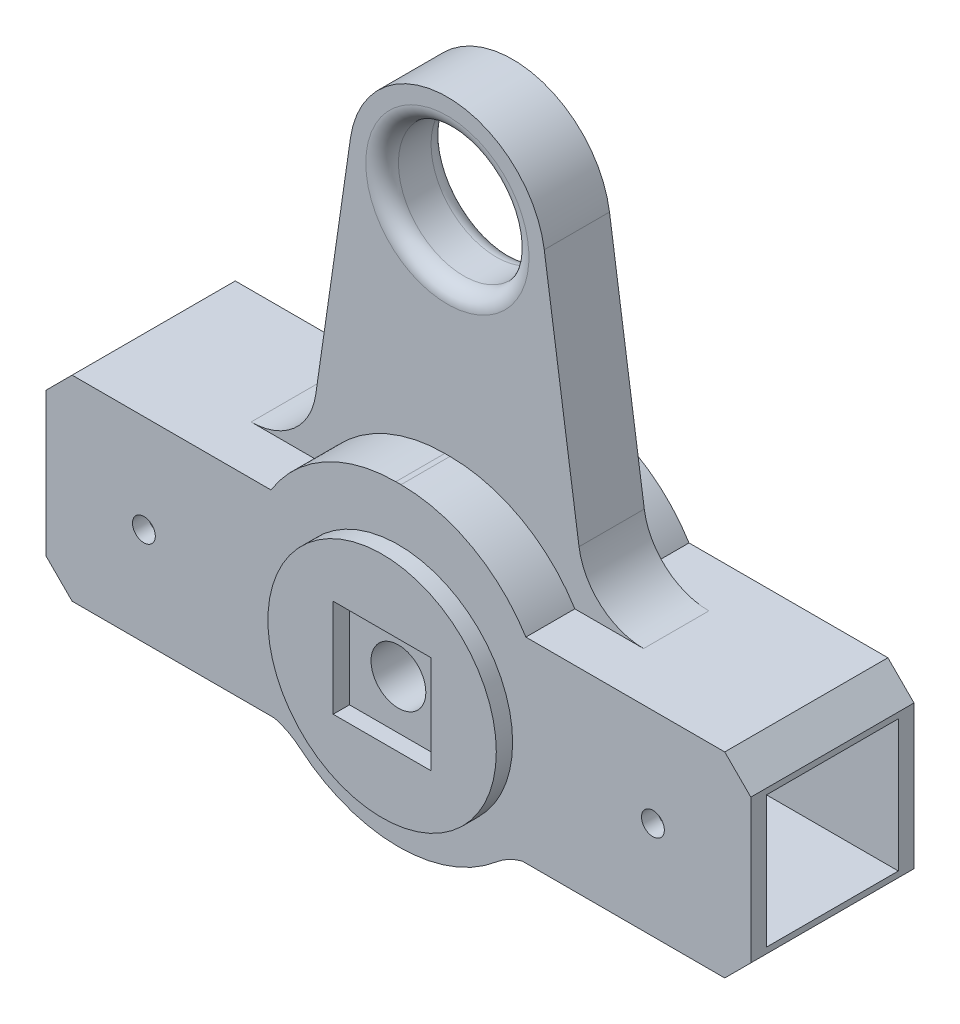
SolidWorks part; units mm, degrees
ref_plane "Alzado" through (0, 0, 0) normal (0, 0, 1) x (1, 0, 0)
ref_plane "Planta" through (0, 0, 0) normal (0, 1, 0) x (1, 0, 0)
ref_plane "Vista lateral" through (0, 0, 0) normal (1, 0, 0) x (0, 0, -1)
sketch "Croquis1" plane through (0, 0, 0) normal (0, 0, 1) x (1, 0, 0)
  line L0 (0, -17.338) -> (0, 18.662) construction
  line L1 (18, 0.662) -> (-18, 0.662) construction
  line L2 (0, 0.662) -> (0, 58.162) construction
  line L3 (-23.0094, 3.9979) -> (-14.8448, 60.3142)
  line L5 (23.0094, 3.9979) -> (14.8448, 60.3142)
  circle A0 centre (0, 0) radius 15
  arc A6 (14.8448, 60.3142) -> (-14.8448, 60.3142) centre (0, 58.162) ccw
  arc A7 (-23.0094, 3.9979) -> (23.0094, 3.9979) centre (0, 0.662) ccw
  circle A8 centre (0, 58.162) radius 10
  point P7 (0, 0.662)
  point P11 (0, 0.662)
  dimension "D1" = 46.5
  dimension "D2" = 30
  dimension "D6" = 30
  dimension "D7" = 20
  dimension "D3" = 18
  dimension "D5" = 57.5
extrude "Saliente-Extruir1" add sketch "Croquis1" along normal mid plane 25
sketch "Croquis3" plane through (0, 0, 0) normal (1, 0, 0) x (0, 0, -1)
  line L1 (12.5, 73.162) -> (-12.5, 73.162) construction
  line L2 (5, 73.162) -> (5, 25.662)
  line L4 (-5, 25.662) -> (-5, 73.162)
  line L6 (-5, 73.162) -> (-12.5, 73.162)
  line L7 (-12.5, 73.162) -> (-12.5, 25.662)
  line L8 (-12.5, 3.9979) -> (-12.5, 60.3142) construction
  line L9 (-12.5, 25.662) -> (-5, 25.662)
  line L10 (5, 25.662) -> (12.5, 25.662)
  line L11 (12.5, 3.9979) -> (12.5, 60.3142) construction
  line L12 (12.5, 25.662) -> (12.5, 73.162)
  line L13 (12.5, 73.162) -> (5, 73.162)
  dimension "D2" = 47.5
  dimension "D3" = 7.5
  dimension "D4" = 7.5
extrude "Cortar-Extruir2" cut sketch "Croquis3" against normal through all both and the other way through all
fillet "Redondeo3" radius 22.5 4 edges at (-19.8686, 25.662, 8.75) (19.8686, 25.662, 8.75) (-19.8686, 25.662, -8.75) (19.8686, 25.662, -8.75)
sketch "Croquis4" plane through (0, 0, -12.5) normal (0, 0, -1) x (-1, 0, 0)
  line L0 (0, 0) -> (-19, 0) construction
  line L1 (-19, 15) -> (-19, -15)
  line L2 (-19, 15) -> (-54, 15)
  line L3 (-54, 15) -> (-54, -15)
  line L4 (-54, -15) -> (-19, -15)
  line L5 (0, 0) -> (0, 9.1483) construction
  line L6 (54, 15) -> (54, -15)
  line L7 (19, 15) -> (54, 15)
  line L8 (19, 15) -> (19, -15)
  line L9 (54, -15) -> (19, -15)
  line L10 (-54, 0) -> (-39, 0) construction
  circle A0 centre (-39, 0) radius 1.75
  circle A1 centre (39, 0) radius 1.75
  point P6 (-19, 0)
  dimension "D4" = 3.5
  dimension "D1" = 30
  dimension "D2" = 19
  dimension "D3" = 35
  dimension "D5" = 15
extrude "Saliente-Extruir2" add sketch "Croquis4" against normal blind 25
sketch "Croquis5" plane through (54, 0, 0) normal (1, 0, 0) x (0, 0, -1)
  line L1 (-10.1, 10.1) -> (10.1, 10.1)
  line L2 (-10.1, 10.1) -> (-10.1, -10.1)
  line L3 (-10.1, -10.1) -> (10.1, -10.1)
  line L4 (10.1, 10.1) -> (10.1, -10.1)
  line L5 (-10.1, 10.1) -> (10.1, -10.1) construction
  line L6 (-10.1, -10.1) -> (10.1, 10.1) construction
  point P0 (0, 0)
  dimension "D1" = 20.2
  dimension "D2" = 20.2
extrude "Cortar-Extruir3" cut sketch "Croquis5" against normal blind 30
mirror "Simetría1" about plane through (0, 0, 0) normal (1, 0, 0) of "Cortar-Extruir3"
fillet "Redondeo4" radius 10 4 edges at (-19, -12.7381, 0) (19, -12.7381, 0) (21.4144, 15, 0) (-21.4144, 15, 0)
chamfer "Chaflán1" distance 4 angle 45 4 edges at (54, 15, 0) (54, -15, 0) (-54, -15, 0) (-54, 15, 0)
fillet "Redondeo6" radius 2.5 2 edges at (-10, 58.162, 5) (0, 48.162, -5)
sketch "Croquis6" plane through (0, 0, 12.5) normal (0, 0, 1) x (1, 0, 0)
  circle A0 centre (0, 0) radius 11.1
  circle A1 centre (0, 0) radius 17.5
  dimension "D1" = 35
  dimension "D2" = 22.2
extrude "Saliente-Extruir3" add sketch "Croquis6" along normal blind 2.5 and the other way blind 27.5
sketch "Croquis8" plane through (0, 0, 15) normal (0, 0, 1) x (1, 0, 0)
  circle A0 centre (0, 0) radius 17.5
  circle A1 centre (0, 0) radius 4.2
  dimension "D1" = 35
  dimension "D2" = 8.4
extrude "Saliente-Extruir4" add sketch "Croquis8" against normal blind 20
sketch "Croquis9" plane through (0, 0, 15) normal (0, 0, 1) x (1, 0, 0)
  line L1 (-7.5, 7.5) -> (7.5, 7.5)
  line L2 (-7.5, 7.5) -> (-7.5, -7.5)
  line L3 (-7.5, -7.5) -> (7.5, -7.5)
  line L4 (7.5, 7.5) -> (7.5, -7.5)
  line L5 (-7.5, 7.5) -> (7.5, -7.5) construction
  line L6 (-7.5, -7.5) -> (7.5, 7.5) construction
  circle A1 centre (0, 0) radius 4.2
  point P0 (0, 0)
  dimension "D2" = 8.4
  dimension "D1" = 15
extrude "Cortar-Extruir4" cut sketch "Croquis9" against normal blind 2.5 and the other way through all
